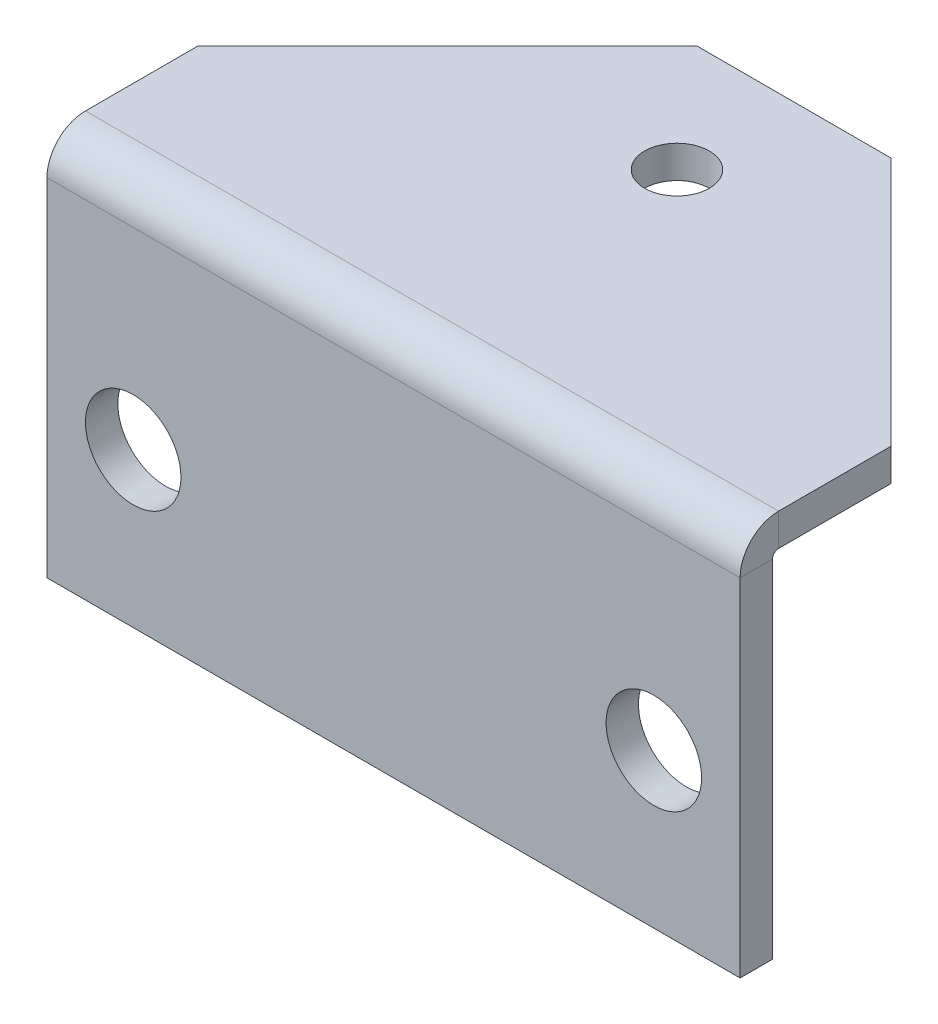
SolidWorks part; units mm, degrees
note: The reader was unsure of these and kept them because the rebuilt part matched: flange length of "Brida de arista1".
ref_plane "Alzado" through (0, 0, 0) normal (0, 0, 1) x (1, 0, 0)
ref_plane "Planta" through (0, 0, 0) normal (0, 1, 0) x (1, 0, 0)
ref_plane "Vista lateral" through (0, 0, 0) normal (1, 0, 0) x (0, 0, -1)
sketch "Croquis1" plane through (0, 0, 0) normal (0, 0, 1) x (1, 0, 0)
  line L7 (-28.575, 15.875) -> (28.575, 15.875)
  line L8 (-28.575, 15.875) -> (-28.575, -15.875)
  line L9 (-28.575, -15.875) -> (28.575, -15.875)
  line L10 (28.575, 15.875) -> (28.575, -15.875)
  line L11 (-28.575, 15.875) -> (28.575, -15.875) construction
  line L12 (-28.575, -15.875) -> (28.575, 15.875) construction
  point P0 (0, 0)
  dimension "D1" = 57.15
  dimension "D2" = 31.75
base flange "Brida base1" sketch "Croquis1" thickness 2.667 reverse thickness direction no parameters "D1"=0.7366
edge flange "Brida de arista1" sketch "Croquis8" flange angle 90 flange length 33.02 flange position material inside bend radius 0.508 thickness 2.667 relief rectangular parameters "D6"=10
sketch "Croquis8" plane through (0, 15.875, -2.667) normal (0, -1, 0) x (-1, 0, 0)
  line L2 (-28.575, 0) -> (-28.575, 30.353)
  line L3 (-28.575, 30.353) -> (28.575, 30.353)
  line L4 (28.575, 30.353) -> (28.575, 0)
  line L5 (28.575, 0) -> (-28.575, 0) construction
  line L6 (28.575, 0) -> (-28.575, 0)
bend "Pliegue de arista1" bend radius 0.508 bend angle 90 parameters "D5"=1
sketch "Croquis9" plane through (0, 0, 0) normal (0, 0, 1) x (1, 0, 0)
  line L0 (0, -15.875) -> (0, 15.875) construction
  line L1 (-28.575, -15.875) -> (28.575, -15.875) construction
  line L2 (-28.575, 15.875) -> (28.575, 15.875) construction
  line L3 (28.575, -15.875) -> (28.575, 12.7) construction
  line L4 (-28.575, 12.7) -> (-28.575, -15.875) construction
  circle A0 centre (-21.463, -3.175) radius 3.937
  circle A1 centre (21.463, -3.175) radius 3.937
  dimension "D2" = 7.874
  dimension "D5" = 7.874
  dimension "D1" = 19.05
  dimension "D3" = 7.112
  dimension "D4" = 19.05
  dimension "D6" = 7.112
extrude "Cortar-Extruir1" cut sketch "Croquis9" against normal blind 5.588 normal cut yes
sketch "Croquis10" plane through (0, 15.875, 0) normal (0, 1, 0) x (1, 0, 0)
  line L0 (-28.575, 33.02) -> (-8.001, 33.02)
  line L1 (-28.575, 33.02) -> (28.575, 33.02) construction
  line L2 (-28.575, 33.02) -> (-28.575, 12.446)
  line L3 (-28.575, 3.175) -> (-28.575, 33.02) construction
  line L4 (-28.575, 12.446) -> (-8.001, 33.02)
  line L5 (28.575, 33.02) -> (8.001, 33.02)
  line L6 (28.575, 33.02) -> (28.575, 12.446)
  line L7 (28.575, 33.02) -> (28.575, 3.175) construction
  line L8 (8.001, 33.02) -> (28.575, 12.446)
  line L9 (28.575, 0) -> (-28.575, 0) construction
  circle A0 centre (0, 23.368) radius 2.667
  dimension "D6" = 5.334
  dimension "D1" = 20.574
  dimension "D2" = 20.574
  dimension "D3" = 20.574
  dimension "D4" = 20.574
  dimension "D5" = 23.368
  dimension "D7" = 28.575
extrude "Cortar-Extruir2" cut sketch "Croquis10" against normal blind 5.588 normal cut yes
sketch "Líneas de pliegue1" [suppressed] plane through (0, 0, 0) normal (0, 1, 0) x (1, 0, 0)
sketch "Cuadro delimitador1" [suppressed] plane through (0, 0, 0) normal (0, 1, 0) x (1, 0, 0)
sheet metal parameters "Chapa metálica1" thickness 2.667 parameters "D1"=0.7366
flat pattern "Chapa desplegada1" [suppressed]
sketch "Líneas de pliegue2" plane through (0, 0, 0) normal (0, 1, 0) x (1, 0, 0)
sketch3d "Cuadro delimitador2" [suppressed]
  line L0 (28.575, -15.875, 0) -> (-28.575, -15.875, 0) construction
  line L1 (28.575, 15.875, 0) -> (-28.575, 15.875, 0) construction
  line L2 (28.575, -15.875, 0) -> (28.575, 15.875, 0) construction
  line L3 (-28.575, -15.875, 0) -> (-28.575, 15.875, 0) construction
sheet metal parameters "Chapa metálica2" thickness 2.667 parameters "D1"=0.7366
flat pattern "Chapa desplegada1"
sketch "Líneas de pliegue2" plane through (0, 0, 0) normal (0, 0, 1) x (1, 0, 0)
  line L0 (28.575, 14.1463) -> (-28.575, 14.1463) construction
  line L1 (28.575, 14.1463) -> (-28.575, 14.1463) construction
sketch3d "Cuadro delimitador2" [suppressed]
  line L0 (28.575, 45.4376, 0) -> (28.575, -15.875, 0) construction
  line L1 (-28.575, 45.4376, 0) -> (-28.575, -15.875, 0) construction
  line L2 (28.575, 45.4376, 0) -> (-28.575, 45.4376, 0) construction
  line L3 (28.575, -15.875, 0) -> (-28.575, -15.875, 0) construction
bend of the flat pattern "Aplanar-<Pliegue de arista1>1"
sheet metal parameters "Chapa metálica3" thickness 2.667 parameters "D1"=0.7366
flat pattern "Chapa desplegada1"
sketch "Líneas de pliegue2" plane through (0, 0, 0) normal (0, 0, 1) x (1, 0, 0)
  line L0 (28.575, 14.1463) -> (-28.575, 14.1463) construction
  line L1 (28.575, 14.1463) -> (-28.575, 14.1463) construction
sketch3d "Cuadro delimitador2" [suppressed]
  line L0 (28.575, 45.4376, 0) -> (28.575, -15.875, 0) construction
  line L1 (-28.575, 45.4376, 0) -> (-28.575, -15.875, 0) construction
  line L2 (28.575, 45.4376, 0) -> (-28.575, 45.4376, 0) construction
  line L3 (28.575, -15.875, 0) -> (-28.575, -15.875, 0) construction
bend of the flat pattern "Aplanar-<Pliegue de arista1>1"
sheet metal parameters "Chapa metálica4" thickness 2.667 parameters "D1"=0.7366
flat pattern "Chapa desplegada1"
sketch "Líneas de pliegue2" plane through (0, 0, 0) normal (0, 0, 1) x (1, 0, 0)
  line L0 (28.575, 13.7274) -> (-28.575, 13.7274) construction
  line L1 (28.575, 13.7274) -> (-28.575, 13.7274) construction
sketch3d "Cuadro delimitador2" [suppressed]
  line L0 (28.575, 44.5998, 0) -> (28.575, -15.875, 0) construction
  line L1 (-28.575, 44.5998, 0) -> (-28.575, -15.875, 0) construction
  line L2 (28.575, 44.5998, 0) -> (-28.575, 44.5998, 0) construction
  line L3 (28.575, -15.875, 0) -> (-28.575, -15.875, 0) construction
bend of the flat pattern "Aplanar-<Pliegue de arista1>1"
